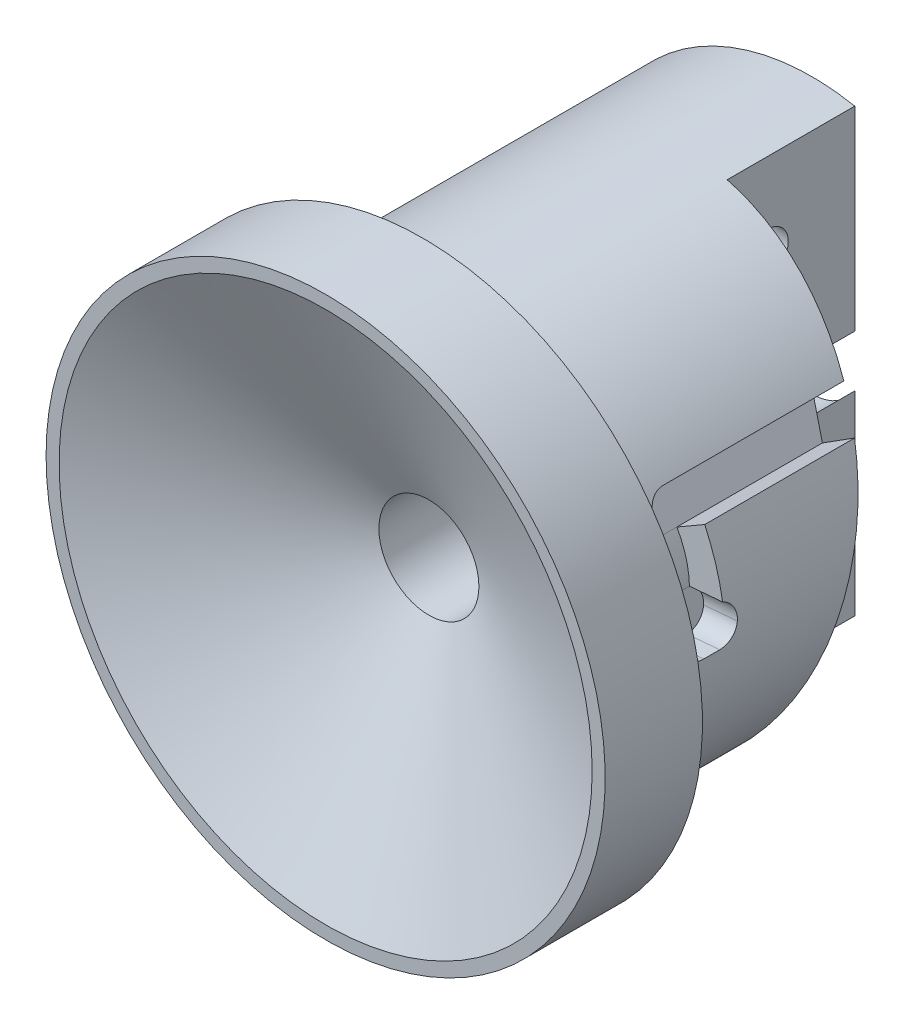
SolidWorks part; units mm, degrees
material "A-2 Steel"
ref_plane "Alzado" through (0, 0, 0) normal (0, 0, 1) x (1, 0, 0)
ref_plane "Planta" through (0, 0, 0) normal (0, 1, 0) x (1, 0, 0)
ref_plane "Vista lateral" through (0, 0, 0) normal (1, 0, 0) x (0, 0, -1)
sketch "Croquis2" plane through (0, 0, 0) normal (1, 0, 0) x (0, 0, -1)
  line L0 (0.3255, 0) -> (-7.0214, 0) construction
  line L1 (0, 3.2639) -> (31.75, 3.2639)
  line L2 (31.75, 3.2639) -> (31.75, 14.6812)
  line L3 (31.75, 14.6812) -> (6.35, 14.6812)
  line L4 (6.35, 14.6812) -> (6.35, 18.2499)
  line L5 (6.35, 18.2499) -> (0, 18.2499)
  line L6 (0, 18.2499) -> (0, 3.2639)
  dimension "D1" = 6.5278
  dimension "D2" = 36.4998
  dimension "D3" = 31.75
  dimension "D4" = 25.4
  dimension "D5" = 29.3624
revolve "Revolución1" add sketch "Croquis2" angle 360 about L0
sketch "Croquis3" plane through (0, 0, 0) normal (0, 1, 0) x (1, 0, 0)
  line L0 (0, 8.2982) -> (-17.399, 0)
  line L2 (-18.2499, 0) -> (18.2499, 0) construction
  line L3 (-17.399, 0) -> (0, 0)
  line L4 (0, 0) -> (0, 8.2982)
  line L5 (0, 0) -> (0, -3.613) construction
  dimension "D1" = 3.613
  dimension "D2" = 34.798
  dimension "D3" = 8.2982
revolve "Cortar-Revolución1" cut sketch "Croquis3" angle 360 about L5
sketch "Croquis4" plane through (0, 0, -31.75) normal (0, 0, -1) x (-1, 0, 0)
  line L0 (-2.794, -14.4129) -> (-2.794, 14.4129)
  circle A1 centre (0, 0) radius 14.6812 construction
  circle A3 centre (0, 0) radius 14.6812
  arc A4 (-2.794, 14.4129) -> (-2.794, -14.4129) centre (0, 0) ccw
  dimension "D1" = 2.794
  dimension "D2" = 0
ref_plane "Plano1" through (2.794, 0, 0) normal (-1, 0, 0) x (0, 1, 0)
sketch "Croquis5" plane through (2.794, 0, 0) normal (-1, 0, 0) x (0, 1, 0)
  line L0 (14.4129, 23.4188) -> (-14.4129, 15.695)
  line L1 (14.4129, 31.75) -> (-14.4129, 31.75) construction
  line L4 (-14.4129, 31.75) -> (-14.4129, 15.695)
  line L6 (14.4129, 23.4188) -> (14.4129, 31.75)
  line L7 (-14.4129, 31.75) -> (14.4129, 31.75) construction
  line L8 (14.4129, 31.75) -> (-14.4129, 31.75)
  dimension "D1" = 15
  dimension "D2" = 8.3312
extrude "Cortar-Extruir1" cut sketch "Croquis5" against normal through all
hole_wizard "Taladro roscado #6-321" positions "Croquis6" profile "Croquis7" tap size "#6-32" standard "Ansi Inch"
sketch "Croquis6" plane through (2.794, 0, 0) normal (1, 0, 0) x (0, 0, -1)
  line L0 (26.0547, 8.9408) -> (31.75, 8.9408) construction
  line L1 (31.75, -14.4129) -> (31.75, 14.4129) construction
  line L3 (0, 0) -> (31.75, 0) construction
  line L5 (20.009, 1.6872) -> (23.4188, 14.4129) construction
  point P0 (26.0547, 8.9408)
  dimension "D1" = 8.9408
  dimension "D2" = 3.9624
sketch "Croquis7" plane through (2.794, 8.9408, -26.0547) normal (0, 1, 0) x (0, 0, -1)
  line L0 (0, 0) -> (0, 11.7855)
  line L1 (0, 11.7855) -> (1.3525, 10.9728)
  line L2 (1.3525, 10.9728) -> (1.3525, 0)
  line L5 (1.3525, 0) -> (0, 0)
  line L10 (0, 11.7855) -> (-1.3526, 10.9728) construction
  line L11 (0, -6.35) -> (0, 107.95) construction
  dimension "Diámetro de perforador para roscar" = 2.7051
  dimension "Profundidad de perforador para roscar" = 10.9728
  dimension "Ángulo de perforador" = 118
cosmetic thread "Rosca de taladro1" parameters "D1"=7.0104, "D2"=3.5052
sketch "Croquis8" plane through (0, 0, -31.75) normal (0, 0, -1) x (-1, 0, 0)
  line L0 (-13.3178, 6.1786) -> (-11.4986, 5.1283)
  line L1 (-11.4986, 5.1283) -> (-10.1905, 7.3939)
  line L2 (-10.1905, 7.3939) -> (-12.0097, 8.4443)
  line L3 (0, 0) -> (-18.2499, 0) construction
  line L4 (0, 0) -> (-15.8049, 9.125) construction
  arc A0 (-2.794, 14.4129) -> (-2.794, -14.4129) centre (0, 0) ccw construction
  arc A1 (-12.0097, 8.4443) -> (-13.3178, 6.1786) centre (0, 0) ccw
  circle A2 centre (0, 0) radius 18.2499 construction
  point P12 (-10.8445, 6.2611)
  point P13 (-12.7143, 7.3406)
  dimension "D1" = 30
  dimension "D2" = 2.6162
  dimension "D3" = 2.159
extrude "Cortar-Extruir2" cut sketch "Croquis8" against normal offset from surface (22.9362 mm away) 2.4638 up to face at (-18.2499, 0, -6.35)
sketch "Croquis9" plane through (0, 0, -8.8138) normal (0, 0, -1) x (-1, 0, 0)
  line L0 (-10.8445, 6.2611) -> (0, 0) construction
  line L1 (-10.1905, 7.3939) -> (-11.4986, 5.1283) construction
  line L2 (0, 0) -> (-18.2499, 0) construction
  line L3 (0, 0) -> (-18.1805, 1.5906) construction
  line L5 (-12.3024, 2.3894) -> (-12.5304, -0.2168)
  line L6 (-12.5304, -0.2168) -> (-14.6812, -0.0287)
  line L7 (-11.0956, 5.8262) -> (-11.4986, 5.1283) construction
  line L8 (-11.0956, 5.8262) -> (-12.9579, 6.9014)
  circle A0 centre (0, 0) radius 18.2499 construction
  arc A1 (-13.3178, 6.1786) -> (-2.794, -14.4129) centre (0, 0) ccw construction
  circle A2 centre (0, 0) radius 14.6812 construction
  arc A3 (-13.7662, 5.102) -> (-14.6812, -0.0287) centre (0, 0) ccw construction
  arc A4 (-11.0956, 5.8262) -> (-12.3024, 2.3894) centre (0, 0) ccw
  arc A5 (-12.9579, 6.9014) -> (-14.6812, -0.0287) centre (0, 0) ccw
  arc A6 (-12.0097, 8.4443) -> (-13.3178, 6.1786) centre (0, 0) ccw construction
  point P12 (-12.4164, 1.0863)
  point P15 (-14.4532, 2.5776)
  arc M11 (-12.0097, 8.4443) -> (-13.3178, 6.1786) centre (0, 0) ccw
  line M12 (-13.3178, 6.1786) -> (-11.4986, 5.1283)
  line M13 (-11.4986, 5.1283) -> (-10.1905, 7.3939)
  dimension "D1" = 25
  dimension "D2" = 2.6162
  dimension "D3" = 2.159
  dimension "D4" = 2.159
extrude "Cortar-Extruir3" cut sketch "Croquis9" along normal blind 2.6162 contours A5 L6 L5 A4 M12 M13 | L8 M13 M11 M12 region at (13.2214, 2.7992, -8.8138) region at (12.2183, 6.0109, -8.8138)
sketch "Croquis10" plane through (12.4164, 1.0863, 0) normal (0.9962, 0.0872, 0) x (0, 0, -1)
  line L0 (8.8138, 1.3081) -> (8.8138, -1.3081) construction
  line L1 (12.2428, -0.0974) -> (10.9347, -0.0974) construction
  line L3 (11.43, -1.3081) -> (11.43, 1.1133)
  arc A0 (11.43, -1.3081) -> (11.43, 1.1133) centre (10.9347, -0.0974) ccw
  dimension "D1" = 3.429
  dimension "D2" = 2.6162
extrude "Cortar-Extruir4" cut sketch "Croquis10" along normal through all
fillet "Redondeo1" radius 1.1938 2 edges at (11.1001, 7.9191, -8.8138) (13.6058, -0.1227, -8.8138)
sketch "Croquis11" plane through (0, 0, -11.43) normal (0, 0, 1) x (1, 0, 0)
  line L0 (10.1905, 7.3939) -> (11.4986, 5.1283) construction
  line L1 (11.0956, 5.8262) -> (11.4986, 5.1283)
  line L2 (12.5304, -0.2168) -> (12.3193, 2.1954) construction
  line L3 (12.3024, 2.3894) -> (12.3193, 2.1954)
  arc A0 (12.3193, 2.1954) -> (11.4986, 5.1283) centre (6.1834, 2.0595) ccw
  arc A10 (12.3024, 2.3894) -> (11.0956, 5.8262) centre (0, 0) ccw
  arc A11 (12.3024, 2.3894) -> (11.0956, 5.8262) centre (0, 0) ccw construction
extrude "Saliente-Extruir1" add sketch "Croquis11" along normal up to surface (2.6162 mm away) up to face at (12.3975, 4.0516, -8.8138)
fillet "Redondeo2" radius 1.1938 1 edges at (13.6058, -0.1227, -11.43)
